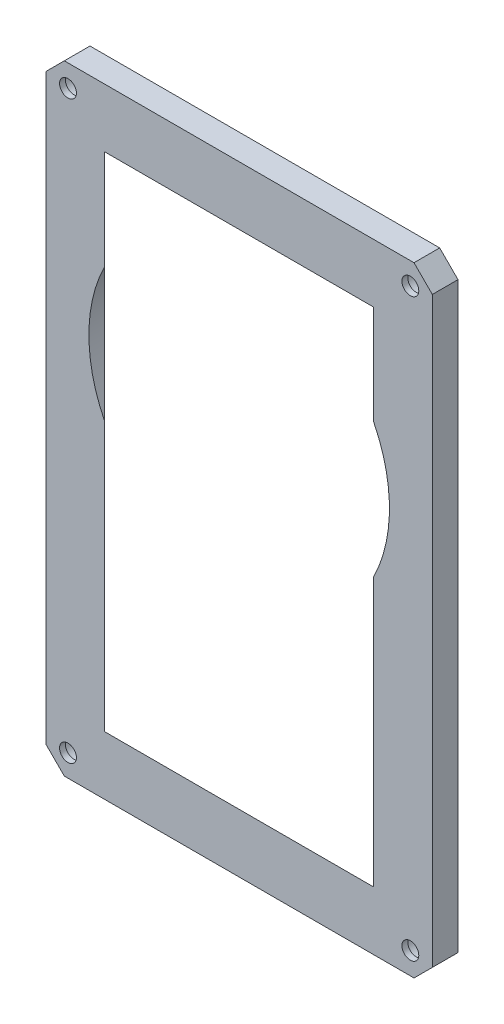
SolidWorks part; units mm, degrees
ref_plane "Plan de face" through (0, 0, 0) normal (0, 0, 1) x (1, 0, 0)
ref_plane "Plan de dessus" through (0, 0, 0) normal (0, 1, 0) x (1, 0, 0)
ref_plane "Plan de droite" through (0, 0, 0) normal (1, 0, 0) x (0, 0, -1)
sketch "Esquisse1" plane through (0, 0, 0) normal (0, 0, 1) x (1, 0, 0)
  line L0 (-52.7, 84.5) -> (52.7, -84.5) construction
  line L1 (-52.7, 84.5) -> (52.7, 84.5)
  line L2 (-52.7, 84.5) -> (-52.7, -84.5)
  line L3 (-52.7, -84.5) -> (52.7, -84.5)
  line L4 (52.7, 84.5) -> (52.7, -84.5)
  line L5 (-34.7, 66.5) -> (34.7, 66.5)
  line L10 (34.7, 66.5) -> (34.7, -66.5)
  line L11 (-34.7, -66.5) -> (34.7, -66.5)
  line L12 (-34.7, 66.5) -> (-34.7, -66.5)
  point P4 (0, 0)
  dimension "D1" = 105.4
  dimension "D2" = 169
  dimension "D3" = 18
extrude "Boss.-Extru.1" add sketch "Esquisse1" against normal blind 7
chamfer "Chanfrein4" distance 5 angle 45 4 edges at (-52.7, -84.5, -3.5) (52.7, -84.5, -3.5) (52.7, 84.5, -3.5) (-52.7, 84.5, -3.5)
chamfer "Chanfrein3" distance 9 angle 45 5 edges at (0, -66.5, -7) (-34.7, 0, -7) (0, 66.5, -7) (34.7, 0, -7) (0, -66.5, 0)
sketch "Esquisse2" plane through (0, 0, 0) normal (0, 0, 1) x (1, 0, 0)
  line L0 (-47.7, 84.5) -> (-52.7, 79.5) construction
  line L1 (-52.7, 79.5) -> (-52.7, -79.5) construction
  line L2 (47.7, 84.5) -> (-47.7, 84.5) construction
  line L3 (-47.7, 84.5) -> (-52.7, 79.5)
  line L4 (-52.7, 79.5) -> (-52.7, -79.5)
  line L5 (47.7, 84.5) -> (-47.7, 84.5)
  line L6 (-36.7, 0) -> (36.7, 0) construction
  line L7 (-36.7, 68.5) -> (-36.7, -68.5) construction
  line L8 (36.7, -68.5) -> (36.7, 68.5) construction
  line L9 (0, 68.5) -> (0, -68.5) construction
  line L10 (36.7, 68.5) -> (-36.7, 68.5) construction
  line L11 (-36.7, -68.5) -> (36.7, -68.5) construction
  circle A0 centre (-46.7, 78.5) radius 2.3
  circle A1 centre (-46.7, -78.5) radius 2.3
  circle A2 centre (46.7, -78.5) radius 2.3
  circle A3 centre (46.7, 78.5) radius 2.3
  dimension "D1" = 4.6
  dimension "D2" = 6
  dimension "6" = 6
extrude "Enlèv. mat.-Extru.1" cut sketch "Esquisse2" against normal up to next contours A0 | A3 | A1 | A2
sketch "Esquisse5" plane through (0, 0, -7) normal (0, 0, -1) x (-1, 0, 0)
  line L0 (0, 84.5) -> (0, -84.5) construction
  line L1 (-47.7, 84.5) -> (47.7, 84.5) construction
  line L2 (47.7, -84.5) -> (-47.7, -84.5) construction
  line L3 (-52.7, 0) -> (52.7, 0) construction
  line L4 (-52.7, -79.5) -> (-52.7, 79.5) construction
  line L5 (52.7, 79.5) -> (52.7, -79.5) construction
  circle A0 centre (-46.7, -78.5) radius 2.3 construction
  circle A1 centre (46.7, -78.5) radius 2.3 construction
  circle A2 centre (46.7, 78.5) radius 2.3 construction
  circle A3 centre (-46.7, 78.5) radius 2.3 construction
  circle A4 centre (-46.7, -78.5) radius 2.3
  circle A5 centre (46.7, -78.5) radius 2.3
  circle A6 centre (46.7, 78.5) radius 2.3
  circle A7 centre (-46.7, 78.5) radius 2.3
  circle A8 centre (-46.7, 78.5) radius 3.7
  circle A9 centre (46.7, 78.5) radius 3.7
  circle A10 centre (46.7, -78.5) radius 3.7
  circle A11 centre (-46.7, -78.5) radius 3.7
  dimension "D1" = 7.4
extrude "Enlèv. mat.-Extru.4" cut sketch "Esquisse5" against normal blind 5.4
sketch "Esquisse4" plane through (0, 0, 0) normal (0, 0, 1) x (1, 0, 0)
  circle A0 centre (0, 23.1) radius 41
  dimension "D2" = 82
  dimension "D1" = 23.1
extrude "Enlèv. mat.-Extru.3" cut sketch "Esquisse4" against normal up to next
